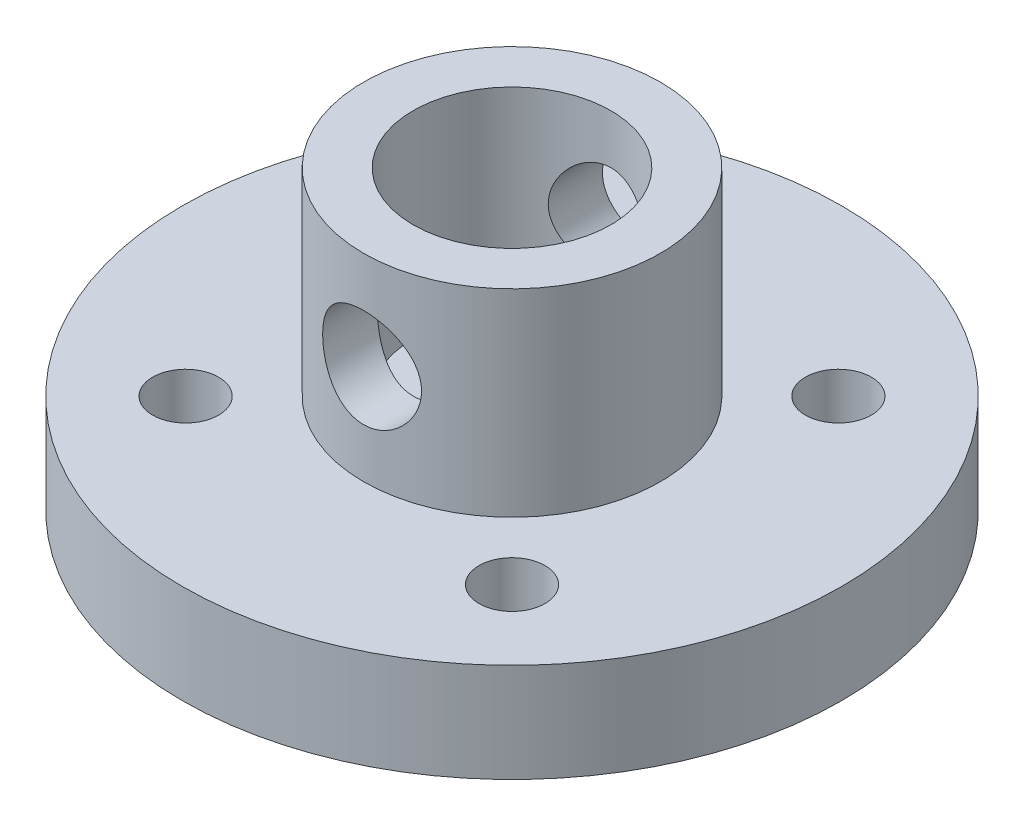
SolidWorks part; units mm, degrees
ref_plane "Alzado" through (0, 0, 0) normal (0, 0, 1) x (1, 0, 0)
ref_plane "Planta" through (0, 0, 0) normal (0, 1, 0) x (1, 0, 0)
ref_plane "Vista lateral" through (0, 0, 0) normal (1, 0, 0) x (0, 0, -1)
sketch "Croquis1" plane through (0, 0, 0) normal (0, 1, 0) x (1, 0, 0)
  line L0 (0, 0) -> (-6.6149, 6.6149) construction
  line L1 (-6.6149, 6.6149) -> (7.3418, -7.3418) construction
  line L2 (0, 0) -> (-6.786, -6.786) construction
  line L3 (-6.786, -6.786) -> (7.1299, 7.1299) construction
  circle A0 centre (0, 0) radius 10
  circle A1 centre (-4.9497, 4.9497) radius 1
  circle A5 centre (0, 0) radius 3
  circle A7 centre (4.9497, 4.9497) radius 1
  circle A8 centre (4.9497, -4.9497) radius 1
  circle A9 centre (-4.9497, -4.9497) radius 1
  circle A10 centre (0, 0) radius 4.5
  point P14 (-1.6569, -4)
  point P23 (0, 0)
  dimension "D1" = 20
  dimension "D2" = 2
  dimension "D4" = 7
  dimension "D5" = 6
  dimension "D6" = 9
  dimension "D7" = 45
  dimension "D3" = 4
extrude "Saliente-Extruir1" add sketch "Croquis1" along normal blind 3 contours A0 A1 | A5 | A5 region at (-9.7172, 0, 0) region at (0, 0, 0) region at (-4.3727, 0, 0)
extrude "Saliente-Extruir2" add sketch "Croquis1<3>" along normal blind 6 from surface contours A10 A5 starting at face at (-4.9497, 3, 5.9497)
sketch "Croquis1<3>" plane through (0, 0, 0) normal (0, 1, 0) x (1, 0, 0) same geometry as "Croquis1"
sketch "Croquis2" plane through (0, 0, 0) normal (0, 0, 1) x (1, 0, 0)
  line L0 (4.5, 9) -> (-4.5, 9) construction
  line L1 (4.5, 3) -> (4.5, 9) construction
  circle A0 centre (0, 6) radius 1.5
  dimension "D2" = 4.5
  dimension "D3" = 3
  dimension "D1" = 3
extrude "Cortar-Extruir1" cut sketch "Croquis2" against normal through all both and the other way through all
